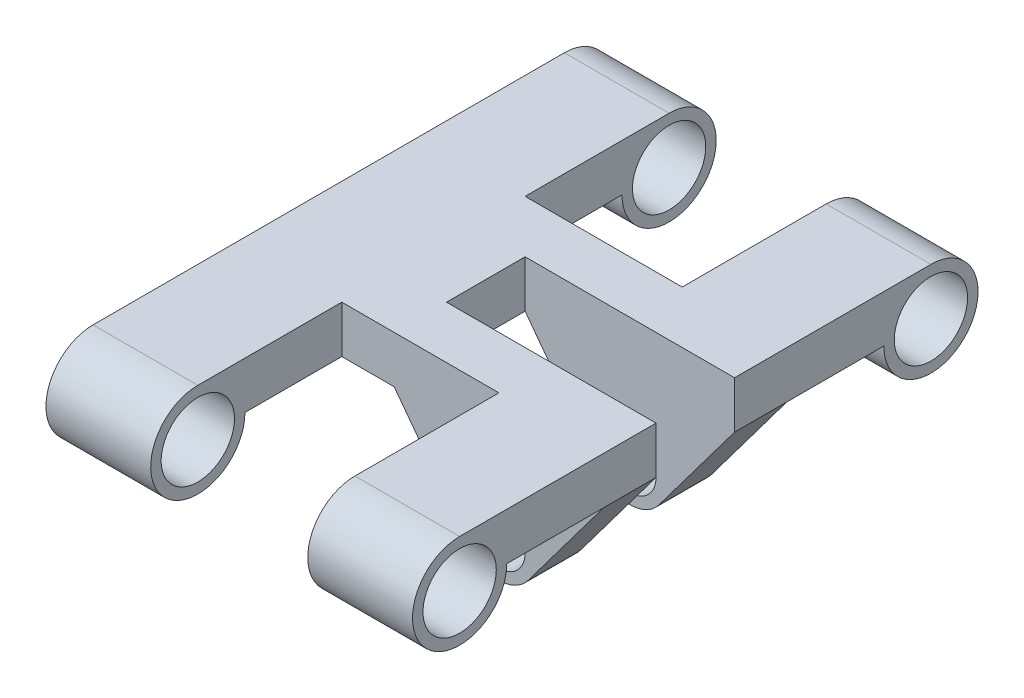
SolidWorks part; units mm, degrees
material "7050-T73510"
ref_plane "Ön Düzlem" through (0, 0, 0) normal (0, 0, 1) x (1, 0, 0)
ref_plane "Üst Düzlem" through (0, 0, 0) normal (0, 1, 0) x (1, 0, 0)
ref_plane "Sağ Düzlem" through (0, 0, 0) normal (1, 0, 0) x (0, 0, -1)
sketch "Sketch1" plane through (0, 0, 0) normal (1, 0, 0) x (0, 0, -1)
  line L0 (0, 9) -> (90.3001, 9)
  line L1 (9, 0) -> (81, 0)
  circle A0 centre (0, 0) radius 7
  circle A1 centre (90, 0) radius 7
  circle A2 centre (0, 0) radius 9
  circle A3 centre (90, 0) radius 9
  dimension "D1" = 14
  dimension "D2" = 14
  dimension "D4" = 18
  dimension "D5" = 18
  dimension "D3" = 90
extrude "Boss-Extrude1" add sketch "Sketch1" against normal blind 20 contours A3 L0 A2 L1 | A2 A0 | A3 A1 region at (0, 4.6268, -45) region at (0, 6.184, -6.184) region at (0, 6.184, -96.184)
sketch "Sketch2" plane through (0, 9, 0) normal (0, 1, 0) x (1, 0, 0)
  line L0 (0, 62.5) -> (50, 62.5)
  line L1 (0, 0) -> (0, 90) construction
  line L2 (50, 62.5) -> (50, 52.5)
  line L3 (50, 52.5) -> (10, 52.5)
  line L4 (10, 52.5) -> (10, 37.5)
  line L5 (10, 37.5) -> (50, 37.5)
  line L6 (50, 37.5) -> (50, 27.5)
  line L7 (50, 27.5) -> (0, 27.5)
  line L8 (0, 27.5) -> (0, 62.5)
  dimension "D1" = 10
  dimension "D2" = 27.5
  dimension "D3" = 15
  dimension "D4" = 50
  dimension "D5" = 40
extrude "Boss-Extrude2" add sketch "Sketch2" against normal up to surface (9 mm away) up to face at (-10, 0, -45)
sketch "Sketch3" plane through (50, 0, 0) normal (1, 0, 0) x (0, 0, -1)
  line L0 (0, 9) -> (90, 9)
  line L1 (9, 0) -> (81, 0)
  line L2 (52.5, 9) -> (52.5, 0)
  line L3 (37.5, 9) -> (37.5, 0)
  circle A0 centre (0, 0) radius 7
  circle A1 centre (0, 0) radius 9
  circle A2 centre (90, 0) radius 7
  circle A3 centre (90, 0) radius 9
  line M2 (27.5, 9) -> (27.5, 0)
  dimension "D1" = 14
  dimension "D2" = 18
  dimension "D3" = 90
extrude "Boss-Extrude4" add sketch "Sketch3" against normal blind 20 contours A1 A0 | A1 L1 L0 M2 | A3 L0 L2 L1 | A3 A2 region at (50, 4.7354, -17.1855) region at (50, 6.184, -6.184) region at (50, 4.658, -67.782) region at (50, 6.184, -96.184)
sketch "Sketch6" plane through (0, 0, -52.5) normal (0, 0, 1) x (1, 0, 0)
  line L0 (10, 0) -> (24.4, -19.2)
  line L1 (50, 0) -> (35.6, -19.2)
  line L4 (10, 0) -> (50, 0) construction
  line L5 (10, 0) -> (50, 0)
  arc A0 (24.4, -19.2) -> (35.6, -19.2) centre (30, -15) ccw
  circle A1 centre (30, -15) radius 5
  dimension "D1" = 7
  dimension "D2" = 10
  dimension "D3" = 15
extrude "Boss-Extrude7" add sketch "Sketch6" against normal up to surface (10 mm away) up to face at (15, 4.5, -62.5)
extrude "Boss-Extrude8" add sketch "Sketch6<3>" along normal up to surface (25 mm away) from offset 15 up to face at (15, 4.5, -27.5)
sketch "Sketch6<3>" plane through (0, 0, -52.5) normal (0, 0, 1) x (1, 0, 0) same geometry as "Sketch6"
